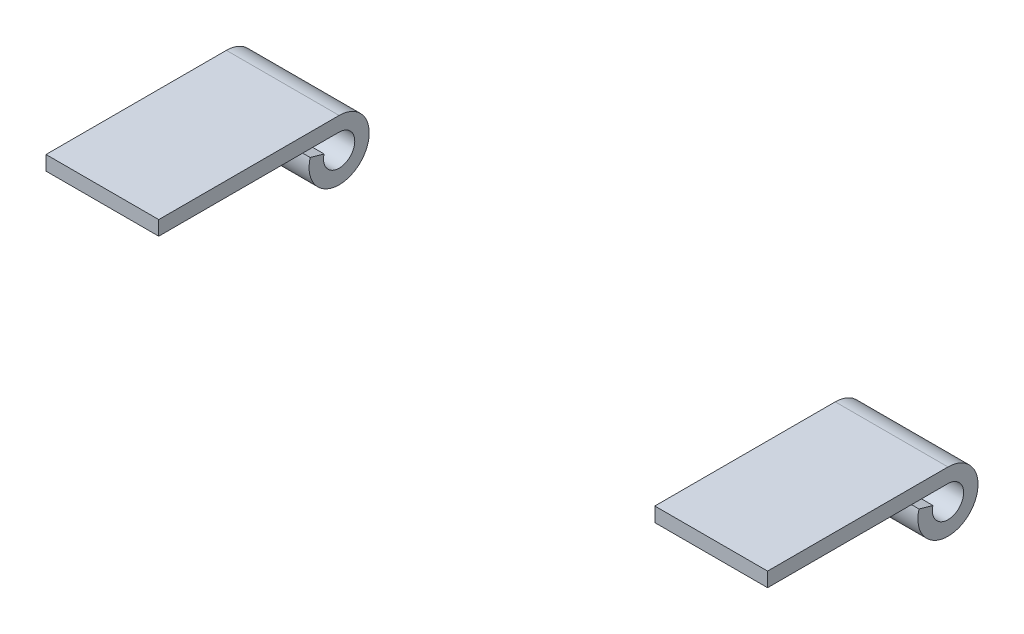
SolidWorks part; units mm, degrees
note: The reader was unsure of these and kept them because the rebuilt part matched: shared geometry of "Sketch1<2>".
ref_plane "Front Plane" through (0, 0, 0) normal (0, 0, 1) x (1, 0, 0)
ref_plane "Top Plane" through (0, 0, 0) normal (0, 1, 0) x (1, 0, 0)
ref_plane "Right Plane" through (0, 0, 0) normal (1, 0, 0) x (0, 0, -1)
sketch "Sketch1" plane through (0, 0, 0) normal (1, 0, 0) x (0, 0, -1)
  line L0 (1540.7863, -31.496) -> (1464.5863, -31.496)
  line L1 (1464.5863, -31.496) -> (1464.5863, -25.4)
  line L2 (1553.5907, -25.4) -> (971.0941, -25.4) construction
  line L3 (1464.5863, -25.4) -> (1540.7863, -25.4)
  line L4 (1528.558, -34.671) -> (1534.4276, -36.3169)
  circle A0 centre (1540.7863, -38.1) radius 6.604 construction
  circle A1 centre (1540.7863, -38.1) radius 6.35 construction
  arc A2 (1540.7863, -25.4) -> (1528.558, -34.671) centre (1540.7863, -38.1) cw
  arc A3 (1540.7863, -31.496) -> (1534.4276, -36.3169) centre (1540.7863, -38.1) cw
  dimension "D1" = 0.254
  dimension "D2" = 3.175
  dimension "D3" = 76.2
extrude "Boss-Extrude1" add sketch "Sketch1" against normal offset from surface (47.625 mm away) 3.175 from surface
extrude "Boss-Extrude2" add sketch "Sketch1<2>" along normal offset from surface (47.625 mm away) 3.175 from surface separate body
sketch "Sketch1<2>" plane through (0, 0, 0) normal (1, 0, 0) x (0, 0, -1) same geometry as "Sketch1"
